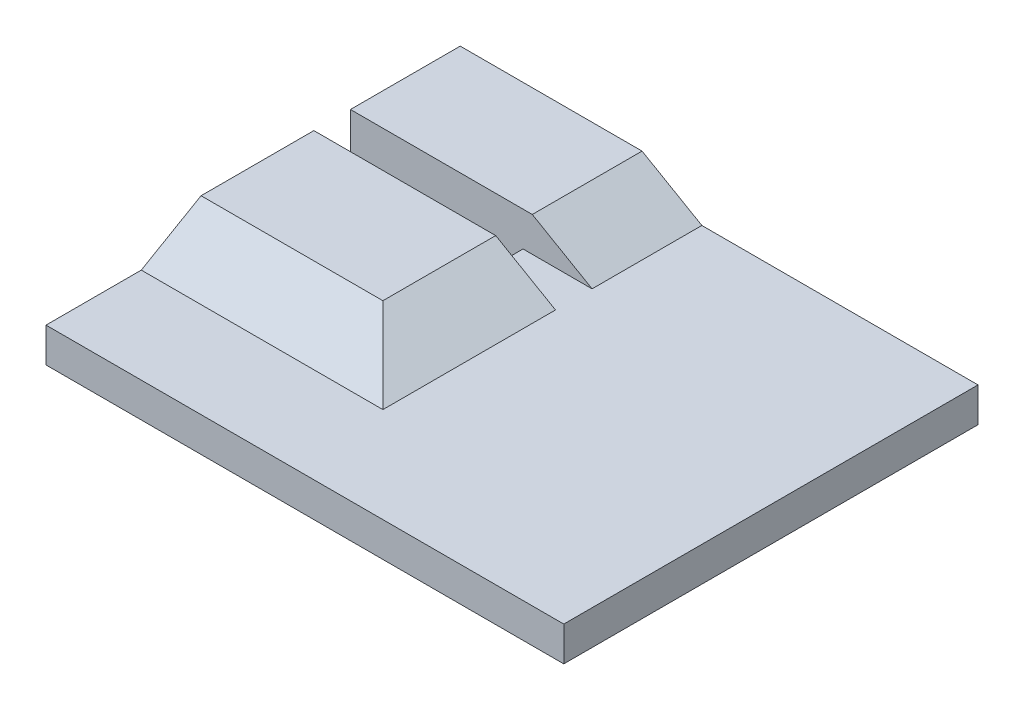
SolidWorks part; units mm, degrees
ref_plane "Front Plane" through (0, 0, 0) normal (0, 0, 1) x (1, 0, 0)
ref_plane "Top Plane" through (0, 0, 0) normal (0, 1, 0) x (1, 0, 0)
ref_plane "Right Plane" through (0, 0, 0) normal (1, 0, 0) x (0, 0, -1)
sketch "Sketch1" plane through (0, 0, 0) normal (0, 1, 0) x (1, 0, 0)
  line L1 (-18.75, -20) -> (18.75, -20)
  line L2 (-18.75, -20) -> (-18.75, 20)
  line L3 (-18.75, 20) -> (18.75, 20)
  line L4 (18.75, -20) -> (18.75, 20)
  line L5 (-18.75, -20) -> (18.75, 20) construction
  line L6 (-18.75, 20) -> (18.75, -20) construction
  point P0 (0, 0)
  dimension "D1" = 40
  dimension "D2" = 37.5
extrude "Boss-Extrude1" add sketch "Sketch1" along normal blind 2.5
sketch "Sketch2" plane through (0, 0, 0) normal (0, -1, 0) x (1, 0, 0)
  line L0 (-18.75, -20) -> (-18.75, 20) construction
  line L1 (-18.75, 0.6) -> (-6.25, 0.6)
  line L2 (-18.75, 0.6) -> (-18.75, -2.05)
  line L3 (-18.75, -2.05) -> (-6.25, -2.05)
  line L4 (-6.25, 0.6) -> (-6.25, -2.05)
  point P4 (0, 0)
  point P5 (0, 0)
  point P8 (0, 0)
  dimension "D1" = 2.65
  dimension "D2" = 12.5
  dimension "D3" = 0.6
extrude "Cut-Extrude1" cut sketch "Sketch2" against normal through all
sketch "Sketch3" plane through (0, 2.5, 0) normal (0, 1, 0) x (1, 0, 0)
  line L0 (18.75, 20) -> (-18.75, 20) construction
  line L1 (-18.75, 2.05) -> (-6.25, 2.05)
  line L2 (-18.75, 2.05) -> (-18.75, 20)
  line L3 (-18.75, 20) -> (-6.25, 20)
  line L4 (-6.25, 2.05) -> (-6.25, 20)
  line L5 (-6.25, 2.05) -> (-6.25, -0.6) construction
  line L7 (-18.75, -0.6) -> (-6.25, -0.6)
  line L8 (-18.75, -0.6) -> (-18.75, -8.1)
  line L9 (-18.75, -8.1) -> (-6.25, -8.1)
  line L10 (-6.25, -0.6) -> (-6.25, -8.1)
  point P13 (0, 0)
  dimension "D1" = 7.5
extrude "Boss-Extrude2" add sketch "Sketch3" along normal blind 2.5
sketch "Sketch4" plane through (0, 5, 0) normal (0, 1, 0) x (1, 0, 0)
  line L1 (-18.75, 20) -> (18.75, 20)
  line L2 (-18.75, 20) -> (-18.75, 10)
  line L3 (-18.75, 10) -> (18.75, 10)
  line L4 (18.75, 20) -> (18.75, 10)
  line L5 (18.75, -20) -> (18.75, 20) construction
  point P7 (0, 0)
  dimension "D1" = 10
extrude "Cut-Extrude2" cut sketch "Sketch4" against normal through all
chamfer "Chamfer1" distance 5 angle 30 3 edges at (-6.25, 2.5, -6.025) (-12.5, 2.5, 8.1) (-6.25, 2.5, 4.35) first distance on face at (-3.125, 2.5, 4.3437)
